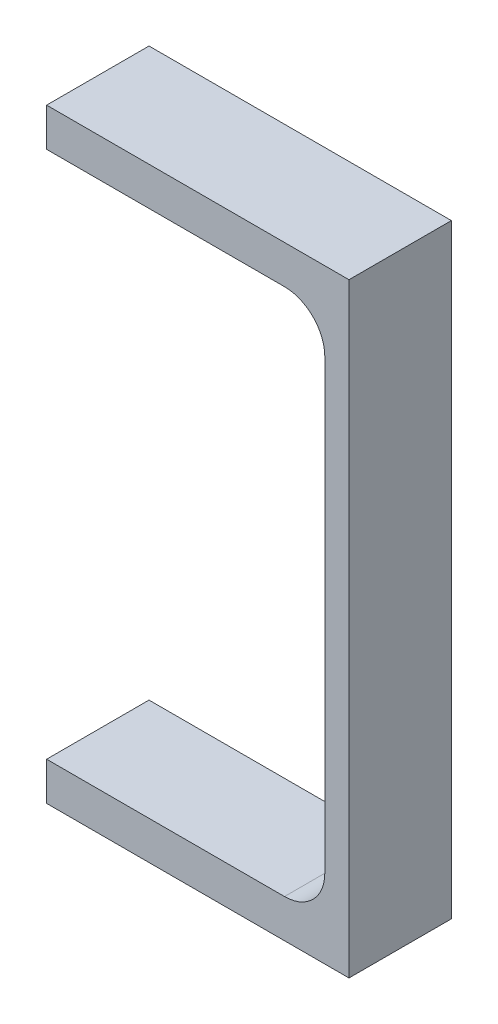
SolidWorks part; units mm, degrees
ref_plane "Front Plane" through (0, 0, 0) normal (0, 0, 1) x (1, 0, 0)
ref_plane "Top Plane" through (0, 0, 0) normal (0, 1, 0) x (1, 0, 0)
ref_plane "Right Plane" through (0, 0, 0) normal (1, 0, 0) x (0, 0, -1)
sketch "Sketch1" plane through (0, 0, 0) normal (0, 0, 1) x (1, 0, 0)
  line L0 (0, 84.7227) -> (0, -104.0799) construction
  line L1 (-75, 75) -> (0, 75)
  line L2 (-75, 75) -> (-75, 65.5)
  line L3 (-75, -75) -> (0, -75)
  line L4 (0, 75) -> (0, -75)
  line L5 (-42.3074, 0) -> (60.8749, 0) construction
  line L6 (-75, -65.5) -> (-75, -75)
  line L7 (-75, 65.5) -> (-16, 65.5)
  line L9 (-75, -65.5) -> (-16, -65.5)
  line L10 (-6, 55.5) -> (-6, -55.5)
  arc A0 (-16, 65.5) -> (-6, 55.5) centre (-16, 55.5) cw
  arc A1 (-16, -65.5) -> (-6, -55.5) centre (-16, -55.5) ccw
  point P18 (0, -75)
  point P27 (0, 75)
  dimension "Radius" = 10
  dimension "Depth" = 150
  dimension "Width" = 75
  dimension "Web_thickness" = 6
  dimension "Thickness" = 9.5
extrude "BaseSection" add sketch "Sketch1" along normal mid plane 25.4
